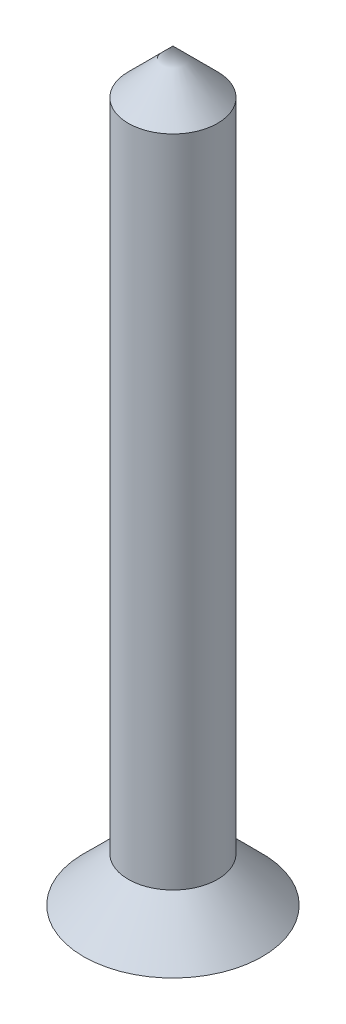
SolidWorks part; units mm, degrees
material "Cast Stainless Steel"
ref_plane "Front Plane" through (0, 0, 0) normal (0, 0, 1) x (1, 0, 0)
ref_plane "Top Plane" through (0, 0, 0) normal (0, 1, 0) x (1, 0, 0)
ref_plane "Right Plane" through (0, 0, 0) normal (1, 0, 0) x (0, 0, -1)
sketch "Sketch1" plane through (0, 0, 0) normal (0, 1, 0) x (1, 0, 0)
  circle A0 centre (0, 0) radius 6
  circle A1 centre (0, 0) radius 3
  dimension "D1" = 12
  dimension "D2" = 6
extrude "Boss-Extrude1" add sketch "Sketch1" along normal blind 3
extrude "Boss-Extrude2" add sketch "Sketch1<2>" along normal blind 50 contours A1 region at (0, 0, 0)
sketch "Sketch1<2>" plane through (0, 0, 0) normal (0, 1, 0) x (1, 0, 0) same geometry as "Sketch1"
chamfer "Chamfer1" distance 3 angle 45 2 edges at (0, 50, 3) (0, 3, 6)
